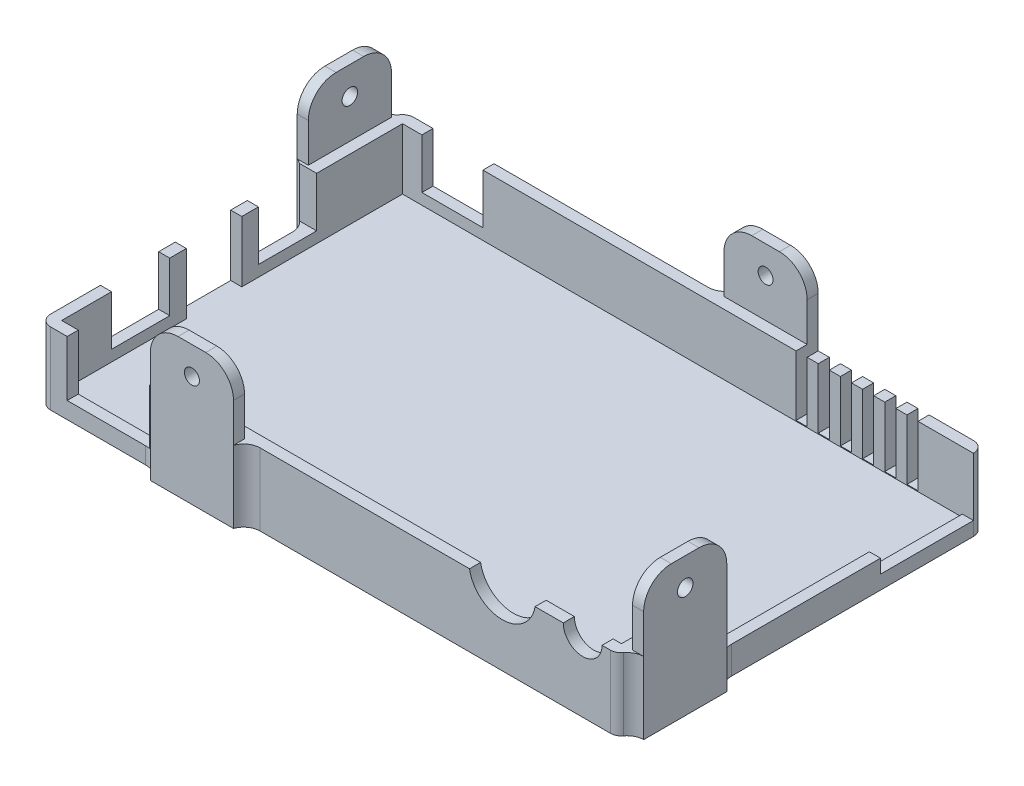
SolidWorks part; units mm, degrees
ref_plane "前视基准面" through (0, 0, 0) normal (0, 0, 1) x (1, 0, 0)
ref_plane "上视基准面" through (0, 0, 0) normal (0, 1, 0) x (1, 0, 0)
ref_plane "右视基准面" through (0, 0, 0) normal (1, 0, 0) x (0, 0, -1)
sketch "草图1" plane through (0, 0, 0) normal (0, 1, 0) x (1, 0, 0)
  line L1 (-52.5, 33) -> (52.5, 33)
  line L2 (-52.5, 33) -> (-52.5, -32.5)
  line L3 (-52.5, -32.5) -> (52.5, -32.5)
  line L4 (52.5, 33) -> (52.5, -32.5)
  dimension "D1" = 65.5
  dimension "D2" = 105
  dimension "D3" = 52.5
  dimension "D4" = 32.5
extrude "凸台-拉伸1" add sketch "草图1" along normal blind 13
shell "抽壳1" thickness 2 removed face at (0, 13, -0.25)
sketch "草图2" plane through (0, 0, 32.5) normal (0, 0, 1) x (1, 0, 0)
  line L0 (-52.5, 13) -> (52.5, 13) construction
  line L1 (-52.5, 0) -> (52.5, 0) construction
  line L2 (-47.5, 13) -> (-32.5, 13)
  line L3 (-47.5, 13) -> (-47.5, 3)
  line L4 (-47.5, 3) -> (-32.5, 3)
  line L5 (-32.5, 13) -> (-32.5, 3)
  line L6 (-52.5, 13) -> (-52.5, 0) construction
  circle A0 centre (45.5, 13) radius 3.5
  circle A1 centre (31, 14) radius 6
  dimension "D1" = 7
  dimension "D2" = 7
  dimension "D3" = 1
  dimension "D4" = 21.5
  dimension "D5" = 3
  dimension "D6" = 5
  dimension "D7" = 20
  dimension "D8" = 10
extrude "切除-拉伸1" cut sketch "草图2" against normal blind 15
sketch "草图3" plane through (-52.5, 0, 0) normal (-1, 0, 0) x (0, 0, 1)
  line L0 (-33, 0) -> (32.5, 0) construction
  line L1 (11, 13) -> (21.5, 13)
  line L2 (11, 13) -> (11, 4)
  line L3 (11, 4) -> (21.5, 4)
  line L4 (21.5, 13) -> (21.5, 4)
  line L5 (32.5, 13) -> (32.5, 0) construction
  line L6 (-33, 13) -> (32.5, 13) construction
  line L7 (-15.5, 13) -> (-5, 13)
  line L8 (-15.5, 13) -> (-15.5, 4)
  line L9 (-15.5, 4) -> (-5, 4)
  line L10 (-5, 13) -> (-5, 4)
  line L12 (-2, 13) -> (8, 13)
  line L13 (-2, 13) -> (-2, 2)
  line L14 (-2, 2) -> (8, 2)
  line L15 (8, 13) -> (8, 2)
  dimension "D1" = 4
  dimension "D2" = 11
  dimension "D3" = 10.5
  dimension "D4" = 9
  dimension "D5" = 16
  dimension "D6" = 10.5
  dimension "D7" = 3
  dimension "D8" = 3
  dimension "D9" = 2
extrude "切除-拉伸2" cut sketch "草图3" against normal blind 15
sketch "草图4" plane through (52.5, 0, 0) normal (1, 0, 0) x (0, 0, -1)
  line L0 (-32.5, 13) -> (33, 13) construction
  line L1 (31, 13) -> (14.2258, 13)
  line L2 (31, 13) -> (31, 2.5)
  line L3 (31, 2.5) -> (14.2258, 2.5)
  line L5 (-32.5, 0) -> (33, 0) construction
  line L6 (-32.5, 13) -> (-32.5, 0) construction
  line L7 (12.965, 13) -> (-15.5, 13)
  line L9 (12.965, 5) -> (-15.5, 5)
  line L10 (-15.5, 13) -> (-15.5, 5)
  line L11 (14.2258, 13) -> (12.965, 13)
  line L12 (12.965, 5) -> (14.2258, 5)
  line L13 (14.2258, 5) -> (14.2258, 2.5)
  dimension "D1" = 2.5
  dimension "D2" = 2
  dimension "D3" = 17
  dimension "D4" = 5
extrude "切除-拉伸3" cut sketch "草图4" against normal blind 15
fillet "圆角1" radius 2 4 edges at (52.5, 6.5, -33) (52.5, 6.5, 32.5) (-52.5, 6.5, 32.5) (-52.5, 6.5, -33)
sketch "草图5" plane through (0, 0, -33) normal (0, 0, -1) x (-1, 0, 0)
  line L0 (-50.5, 13) -> (-50.5, 0) construction
  line L1 (-42.5, 2.1489) -> (-40.5, 2.1489)
  line L2 (-42.5, 2.1489) -> (-42.5, 19.3489)
  line L3 (-42.5, 19.3489) -> (-40.5, 19.3489)
  line L4 (-40.5, 2.1489) -> (-40.5, 19.3489)
  line L5 (-38.5, 2.1489) -> (-38.5, 19.3489)
  line L6 (-38.5, 2.1489) -> (-36.5, 2.1489)
  line L7 (-36.5, 2.1489) -> (-36.5, 19.3489)
  line L8 (-38.5, 19.3489) -> (-36.5, 19.3489)
  line L9 (-34.5, 2.1489) -> (-34.5, 19.3489)
  line L10 (-34.5, 2.1489) -> (-32.5, 2.1489)
  line L11 (-32.5, 2.1489) -> (-32.5, 19.3489)
  line L12 (-34.5, 19.3489) -> (-32.5, 19.3489)
  line L13 (-30.5, 2.1489) -> (-30.5, 19.3489)
  line L14 (-30.5, 2.1489) -> (-28.5, 2.1489)
  line L15 (-28.5, 2.1489) -> (-28.5, 19.3489)
  line L16 (-30.5, 19.3489) -> (-28.5, 19.3489)
  line L17 (-27.5, 20.485) -> (-27.5, -5.3953) construction
  line L18 (-24.5, 19.3489) -> (-26.5, 19.3489)
  line L19 (-26.5, 2.1489) -> (-26.5, 19.3489)
  line L20 (-24.5, 2.1489) -> (-26.5, 2.1489)
  line L21 (-24.5, 2.1489) -> (-24.5, 19.3489)
  line L22 (-20.5, 19.3489) -> (-22.5, 19.3489)
  line L23 (-22.5, 2.1489) -> (-22.5, 19.3489)
  line L24 (-20.5, 2.1489) -> (-22.5, 2.1489)
  line L25 (-20.5, 2.1489) -> (-20.5, 19.3489)
  dimension "D1" = 8
  dimension "D2" = 2
  dimension "D4" = 1
  dimension "D3" = 4
extrude "切除-拉伸4" cut sketch "草图5" against normal blind 15
sketch "草图6" plane through (0, 0, -33) normal (0, 0, -1) x (-1, 0, 0)
  line L0 (-28.5, 13) -> (-26.5, 13) construction
  line L1 (47, 13) -> (36, 13)
  line L2 (47, 13) -> (47, 4)
  line L3 (47, 4) -> (36, 4)
  line L4 (36, 13) -> (36, 4)
  line L5 (-50.5, 0) -> (50.5, 0) construction
  line L6 (50.5, 0) -> (50.5, 13) construction
  dimension "D1" = 4
  dimension "D2" = 3.5
  dimension "D3" = 11
extrude "切除-拉伸5" cut sketch "草图6" against normal blind 15
sketch "草图10" plane through (0, 0, 0) normal (0, -1, 0) x (1, 0, 0)
  line L0 (50.5, -33) -> (-50.5, -33) construction
  line L1 (-52.5, -31) -> (-54.5, -31)
  line L2 (-52.5, -31) -> (-52.5, -16)
  line L3 (-52.5, -16) -> (-54.5, -16)
  line L4 (-54.5, -31) -> (-54.5, -16)
  line L5 (52.5, 30.5) -> (54.5, 30.5)
  line L6 (52.5, 30.5) -> (52.5, 15.5)
  line L7 (52.5, 15.5) -> (54.5, 15.5)
  line L8 (54.5, 30.5) -> (54.5, 15.5)
  line L9 (20.5, -33) -> (5.5, -33)
  line L13 (52.5, 30.5) -> (52.5, -31) construction
  line L14 (5.5, -33) -> (5.5, -35)
  line L15 (20.5, -35) -> (5.5, -35)
  line L16 (20.5, -33) -> (20.5, -35)
  line L17 (-50.5, 32.5) -> (50.5, 32.5) construction
  line L18 (-30.5, 32.5) -> (-15.5, 32.5)
  line L22 (-52.5, -31) -> (-52.5, 30.5) construction
  line L23 (-15.5, 32.5) -> (-15.5, 34.5)
  line L24 (-30.5, 34.5) -> (-15.5, 34.5)
  line L25 (-30.5, 32.5) -> (-30.5, 34.5)
  dimension "D1" = 2
  dimension "D2" = 15
  dimension "D3" = 2
  dimension "D4" = 15
  dimension "D6" = 32
  dimension "D7" = 22
extrude "凸台-拉伸2" add sketch "草图10" against normal blind 25
fillet "圆角2" radius 3 7 edges at (52.5, 6.5, 30.5) (-52.5, 6.5, -31) (-52.5, 6.5, -16) (52.5, 2.5, 15.5) (5.5, 6.5, -33) (-30.5, 6.5, 32.5) (-15.5, 6.5, 32.5)
fillet "圆角3" radius 5 8 edges at (53.5, 25, 15.5) (53.5, 25, 30.5) (-53.5, 25, -31) (-53.5, 25, -16) (-30.5, 25, 33.5) (-15.5, 25, 33.5) (20.5, 25, -34) (5.5, 25, -34)
sketch "草图11" plane through (54.5, 0, 0) normal (1, 0, 0) x (0, 0, -1)
  line L0 (31, 13) -> (16, 13) construction
  circle A0 centre (-23, 20) radius 1.4
  circle A1 centre (23.5, 20) radius 1.4
  dimension "D3" = 2.8
  dimension "D4" = 2.8
  dimension "D1" = 7
  dimension "D2" = 7
extrude "切除-拉伸6" cut sketch "草图11" against normal blind 120
sketch "草图13" plane through (0, 0, -35) normal (0, 0, -1) x (-1, 0, 0)
  line L0 (-20.5, 20) -> (-20.5, 0) construction
  line L2 (30.5, 20) -> (30.5, 13) construction
  line L4 (-2.6716, 13) -> (36, 13) construction
  circle A0 centre (-13, 20) radius 1.35
  circle A1 centre (23, 20) radius 1.35
  point P8 (0, 0)
  dimension "D1" = 7.5
  dimension "D3" = 2.7
  dimension "D4" = 2.7
  dimension "D5" = 7.5
  dimension "D6" = 7
  dimension "D2" = 7
extrude "切除-拉伸7" cut sketch "草图13" against normal blind 76
